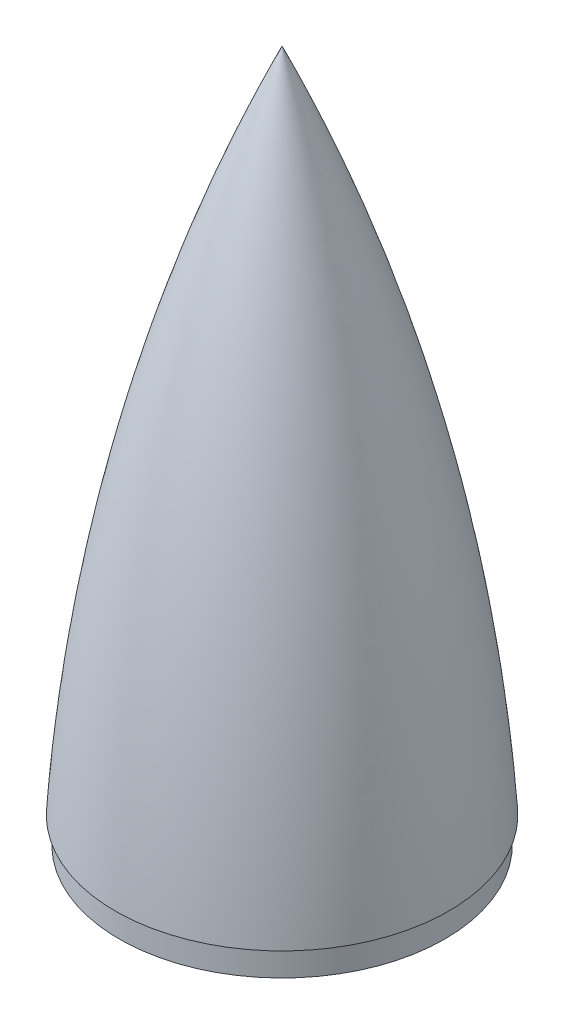
SolidWorks part; units mm, degrees
material "PVB"
ref_plane "Front Plane" through (0, 0, 0) normal (0, 0, 1) x (1, 0, 0)
ref_plane "Top Plane" through (0, 0, 0) normal (0, 1, 0) x (1, 0, 0)
ref_plane "Right Plane" through (0, 0, 0) normal (1, 0, 0) x (0, 0, -1)
sketch "Sketch2" plane through (0, 0, 0) normal (0, 0, 1) x (1, 0, 0)
  line L0 (0, 0) -> (0, 381) construction
  line L1 (-95.4151, 0) -> (-90.3351, 0)
  line L2 (0, 381) -> (0, 375.92)
  arc A0 (0, 381) -> (-95.4151, 0) centre (995.6515, -70.7919) ccw
  arc A1 (0, 375.92) -> (-90.3351, 0) centre (1112.9542, -90.3414) ccw
  dimension "D1" = 381
  dimension "D2" = 5.08
  dimension "D3" = 95.4151
  dimension "D4" = 5.08
revolve "Revolve1" add sketch "Sketch2" angle 360 about L2
sketch "Sketch3" plane through (0, 0, 0) normal (0, -1, 0) x (1, 0, 0)
  circle A0 centre (0, 0) radius 88.9
  circle A1 centre (0, 0) radius 86.995
  dimension "D1" = 177.8
extrude "Boss-Extrude1" [suppressed] add sketch "Sketch3" along normal blind 35.56
sketch "Sketch4" plane through (0, 0, 0) normal (0, -1, 0) x (-1, 0, 0)
  circle A0 centre (0, 0) radius 93.1545
  circle A1 centre (0, 0) radius 89.027
  dimension "D1" = 186.309
  dimension "D2" = 178.054
extrude "Boss-Extrude2" add sketch "Sketch4" along normal blind 15
